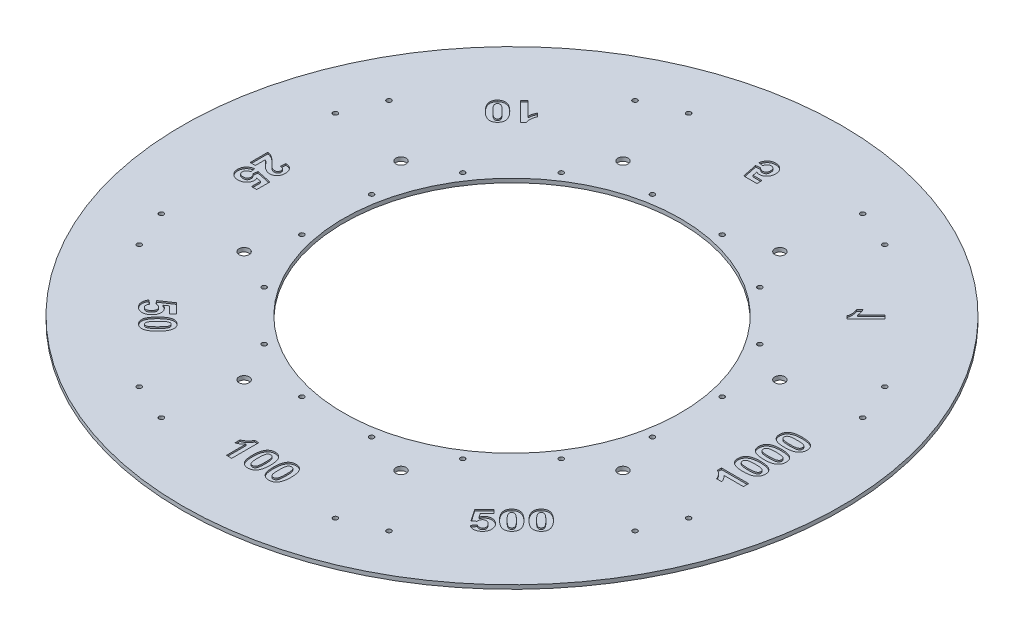
SolidWorks part; units mm, degrees
ref_plane "Plan de face" through (0, 0, 0) normal (0, 0, 1) x (1, 0, 0)
ref_plane "Plan de dessus" through (0, 0, 0) normal (0, 1, 0) x (1, 0, 0)
ref_plane "Plan de droite" through (0, 0, 0) normal (1, 0, 0) x (0, 0, -1)
sketch "Esquisse1" plane through (0, 0, 0) normal (0, 1, 0) x (1, 0, 0)
  circle A0 centre (0, 0) radius 115
  circle A1 centre (0, 0) radius 225
  dimension "D1" = 230
  dimension "D2" = 450
extrude "Boss.-Extru.1" add sketch "Esquisse1" along normal blind 2.7
ref_axis "Axe1" through (0, 26.7531, 0) along (0, -1, 0)
sketch "Esquisse7" plane through (0, 0, 0) normal (0, 1, 0) x (1, 0, 0)
  line L0 (0, 0) -> (0, 182.1463) construction
  line L1 (0, 0) -> (23.801, 119.6558) construction
  line L2 (0, 0) -> (-23.801, 119.6558) construction
  circle A0 centre (-23.801, 119.6558) radius 1.6
  circle A1 centre (23.801, 119.6558) radius 1.6
  dimension "D3" = 3.2
  dimension "D1" = 22.5
  dimension "D2" = 122
extrude "Enlèv. mat.-Extru.6" cut sketch "Esquisse7" along normal through all
pattern_circular "Répétition circulaire3" count 8 over 360 about axis through (0, 26.7531, 0) along (0, -1, 0) of "Enlèv. mat.-Extru.6"
sketch "Esquisse2" [suppressed] plane through (0, 0, 0) normal (0, 1, 0) x (1, 0, 0)
  line L0 (0, 0) -> (0, 225) construction
  line L2 (-46, 209) -> (46, 209)
  line L3 (-46, 209) -> (-46, 127)
  line L4 (-46, 127) -> (46, 127)
  line L5 (46, 209) -> (46, 127)
  line L6 (-46, 209) -> (46, 127) construction
  line L7 (-46, 127) -> (46, 209) construction
  circle A0 centre (0, 0) radius 225 construction
  point P6 (0, 168)
  dimension "D1" = 92
  dimension "D2" = 82
  dimension "D3" = 127
extrude "Enlèv. mat.-Extru.1" [suppressed] cut sketch "Esquisse2" along normal blind 2.7
fillet "Congé1" [suppressed] radius 1
pattern_circular "Répétition circulaire1" [suppressed] count 8 over 360 reverse direction yes of bodies 102
sketch "Esquisse3" [suppressed] plane through (0, 0, 0) normal (0, 1, 0) x (1, 0, 0)
  line L0 (0, 201) -> (0, 0)
  line L1 (0, 0) -> (142.1285, 142.1285)
  line L5 (57.9828, 121.6224) -> (121.6224, 57.9828) construction
  arc A0 (142.1285, 142.1285) -> (0, 201) centre (0, 0) ccw
  circle A2 centre (0, 0) radius 225 construction
  point P13 (89.8026, 89.8026)
  dimension "D1" = 24
  dimension "D2" = 201
extrude "Enlèv. mat.-Extru.2" [suppressed] cut sketch "Esquisse3" along normal blind 2.7 flip side to cut
sketch "Esquisse6" plane through (0, 0, 0) normal (0, 1, 0) x (1, 0, 0)
  line L0 (0, 0) -> (79.3569, 191.5844) construction
  line L1 (59.3929, 179.9708) -> (85.2615, 169.2557) construction
  line L2 (0, 0) -> (0, 197.0359) construction
  circle A1 centre (85.2615, 169.2557) radius 1.6
  circle A2 centre (59.3929, 179.9708) radius 1.6
  point P8 (72.3272, 174.6132)
  dimension "D2" = 3.2
  dimension "D1" = 28
  dimension "D3" = 189
  dimension "D4" = 22.5
extrude "Enlèv. mat.-Extru.5" cut sketch "Esquisse6" along normal through all
pattern_circular "Répétition circulaire2" count 8 over 360 about axis through (0, 26.7531, 0) along (0, -1, 0) of "Enlèv. mat.-Extru.5"
sketch "Esquisse14" plane through (0, 0, 0) normal (0, 1, 0) x (1, 0, 0)
  line L0 (53.5757, 129.3431) -> (0, 0) construction
  line L1 (0, 0) -> (0, 100.3012) construction
  circle A0 centre (0, 0) radius 140 construction
  circle A1 centre (53.5757, 129.3431) radius 3.5
  dimension "D1" = 280
  dimension "D2" = 7
  dimension "D3" = 22.5
extrude "Enlèv. mat.-Extru.12" cut sketch "Esquisse14" along normal through all
pattern_circular "Répétition circulaire6" count 8 over 360 about axis through (0, 26.7531, 0) along (0, -1, 0) of "Enlèv. mat.-Extru.12"
sketch "Esquisse5" [suppressed] plane through (0, 0, 0) normal (0, 1, 0) x (1, 0, 0)
  line L0 (67.735, 163.5267) -> (0, 0)
  line L1 (0, 0) -> (-67.735, 163.5267)
  line L2 (0, 177) -> (0, 0) construction
  arc A0 (67.735, 163.5267) -> (-67.735, 163.5267) centre (0, 0) ccw
  circle A1 centre (0, 0) radius 225 construction
  dimension "D1" = 48
  dimension "D2" = 45
extrude "Enlèv. mat.-Extru.4" [suppressed] cut sketch "Esquisse5" along normal blind 2.7 flip side to cut
fillet "Congé2" [suppressed] radius 4
fillet "Congé3" [suppressed] radius 4
sketch "Esquisse8" plane through (0, 0, 0) normal (0, 1, 0) x (1, 0, 0)
  circle A0 centre (0, 0) radius 115 construction
  circle A1 centre (0, 0) radius 115
  circle A2 centre (0, 0) radius 225 construction
  circle A3 centre (0, 0) radius 225
  circle A4 centre (0, 0) radius 243
  circle A6 centre (0, 0) radius 2.1
  dimension "D4" = 18
  dimension "D5" = 4.2
extrude "Boss.-Extru.2" [suppressed] add sketch "Esquisse8" along normal blind 1 contours A1 A6 | A4 A3
sketch "Esquisse9" [suppressed] plane through (0, 1, 0) normal (0, 1, 0) x (1, 0, 0)
  line L0 (0, 0) -> (0, 243) construction
  line L1 (0, 0) -> (89.3566, 215.7259) construction
  line L3 (-0.5, 258) -> (0.5, 258)
  line L4 (-0.5, 258) -> (-0.5, 228)
  line L5 (-0.5, 228) -> (0.5, 228)
  line L6 (0.5, 258) -> (0.5, 228)
  line L7 (-0.5, 258) -> (0.5, 228) construction
  line L8 (-0.5, 228) -> (0.5, 258) construction
  circle A0 centre (0, 0) radius 243 construction
  circle A1 centre (89.3566, 215.7259) radius 2
  dimension "D3" = 4
  dimension "D1" = 22.5
  dimension "D2" = 233.5
  dimension "D4" = 1
  dimension "D5" = 15
extrude "Enlèv. mat.-Extru.8" [suppressed] cut sketch "Esquisse9" against normal through all
pattern_circular "Répétition circulaire4" [suppressed] count 8 over 360 about axis through (0, 26.7531, 0) along (0, -1, 0) of bodies 112
sketch "Esquisse10" [suppressed] plane through (0, 0, 0) normal (0, 1, 0) x (1, 0, 0)
  line L0 (0, 0) -> (66.468, 66.468) construction
  line L1 (59.397, 73.5391) -> (73.5391, 59.397) construction
  line L2 (0, 0) -> (43.1027, 0) construction
  circle A0 centre (59.397, 73.5391) radius 2
  circle A1 centre (73.5391, 59.397) radius 2
  point P5 (66.468, 66.468)
  dimension "D3" = 4
  dimension "D1" = 20
  dimension "D2" = 94
  dimension "D4" = 45
extrude "Enlèv. mat.-Extru.9" [suppressed] cut sketch "Esquisse10" along normal through all
pattern_circular "Répétition circulaire5" [suppressed] count 4 over 360 about axis through (0, 26.7531, 0) along (0, -1, 0) of bodies 114
sketch "Esquisse11" [suppressed] plane through (0, 1, 0) normal (0, 1, 0) x (1, 0, 0)
  line L0 (0, 0) -> (-85.5, 0) construction
  line L1 (-85.5, 42) -> (-85.5, -42) construction
  circle A0 centre (-31.5, 0) radius 2
  circle A1 centre (-85.5, -42) radius 2
  circle A2 centre (-85.5, 42) radius 2
  dimension "D4" = 4
  dimension "D1" = 84
  dimension "D2" = 31.5
  dimension "D3" = 85.5
extrude "Enlèv. mat.-Extru.11" [suppressed] cut sketch "Esquisse11" against normal through all
sketch "Esquisse13" [suppressed] plane through (0, 2.7, 0) normal (0, 1, 0) x (1, 0, 0)
  line L0 (0, 0) -> (0, 225) construction
  line L2 (-1.5, 228) -> (1.5, 228)
  line L3 (-1.5, 228) -> (-1.5, 112)
  line L4 (-1.5, 112) -> (1.5, 112)
  line L5 (1.5, 228) -> (1.5, 112)
  line L6 (-1.5, 228) -> (1.5, 112) construction
  line L7 (-1.5, 112) -> (1.5, 228) construction
  circle A0 centre (0, 0) radius 225 construction
  point P6 (0, 170)
  dimension "D1" = 170
  dimension "D2" = 116
  dimension "D3" = 3
extrude "Boss.-Extru.3" [suppressed] add sketch "Esquisse13" against normal up to next
sketch "Esquisse15" [suppressed] plane through (0, 0, 0) normal (0, 1, 0) x (1, 0, 0)
  line L0 (136, 18) -> (136, -18) construction
  line L1 (0, 30) -> (142, 30)
  line L2 (0, 30) -> (0, -30)
  line L3 (0, -30) -> (142, -30)
  line L4 (142, 30) -> (142, -30)
  line L5 (0, 0) -> (136, 0) construction
  circle A0 centre (136, 18) radius 1.5
  circle A1 centre (136, -18) radius 1.5
  dimension "D5" = 3
  dimension "D1" = 60
  dimension "D2" = 142
  dimension "D3" = 136
  dimension "D4" = 36
extrude "Enlèv. mat.-Extru.13" [suppressed] cut sketch "Esquisse15" along normal blind 10 flip side to cut
sketch "Esquisse16" [suppressed] plane through (0, 1, 0) normal (0, 1, 0) x (1, 0, 0)
  line L0 (0, 0) -> (75, 0) construction
  line L1 (75, 15) -> (75, -15) construction
  circle A0 centre (75, 15) radius 2
  circle A1 centre (75, -15) radius 2
  dimension "D3" = 4
  dimension "D1" = 75
  dimension "D2" = 30
extrude "Enlèv. mat.-Extru.15" [suppressed] cut sketch "Esquisse16" against normal through all
sketch "Esquisse17" plane through (0, 0, 0) normal (0, 1, 0) x (1, 0, 0)
  line L0 (-180, 0) -> (180, 0) construction
  line L1 (180, 40) -> (180, -40) construction
  line L2 (-180, 40) -> (-180, -40) construction
  line L3 (0, 180) -> (0, -180) construction
  line L4 (-127.2792, 127.2792) -> (127.2792, -127.2792) construction
  line L5 (127.2792, 127.2792) -> (-127.2792, -127.2792) construction
  line L6 (-98.9949, 155.5635) -> (-155.5635, 98.9949) construction
  line L7 (155.5635, -98.9949) -> (98.9949, -155.5635) construction
  line L8 (-155.5635, -98.9949) -> (-98.9949, -155.5635) construction
  line L9 (98.9949, 155.5635) -> (155.5635, 98.9949) construction
  line L10 (-40, 180) -> (40, 180) construction
  line L11 (-40, -180) -> (40, -180) construction
  point P24 (0, 0)
  dimension "D1" = 360
  dimension "D2" = 80
  dimension "D3" = 45
  dimension "D4" = 45
sketch "Esquisse18" plane through (0, 2.7, 0) normal (0, 1, 0) x (1, 0, 0)
  text T0 "1" font "Arial" height in points 72
  text T1 "5" font "Arial" height in points 72
  text T2 "10" font "Arial" height in points 72
  text T3 "25" font "Arial" height in points 72
  text T4 "50" font "Arial" height in points 72
  text T5 "100" font "Arial" height in points 72
  text T6 "500" font "Arial" height in points 72
  text T7 "1000" font "Arial" height in points 72
extrude "Enlèv. mat.-Extru.17" cut sketch "Esquisse18" against normal blind 1
